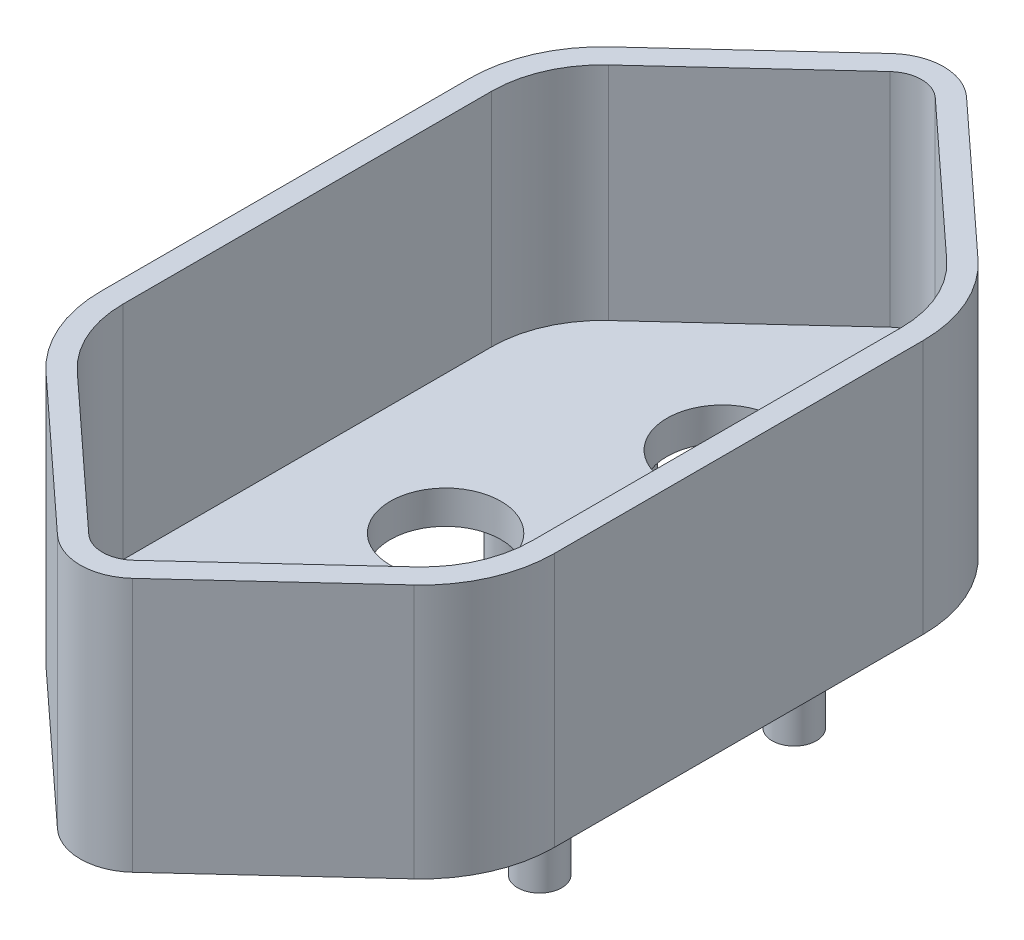
SolidWorks part; units mm, degrees
ref_plane "Plano frontal" through (0, 0, 0) normal (0, 0, 1) x (1, 0, 0)
ref_plane "Plano superior" through (0, 0, 0) normal (0, 1, 0) x (1, 0, 0)
ref_plane "Plano direito" through (0, 0, 0) normal (1, 0, 0) x (0, 0, -1)
sketch "Esboço1" plane through (0, 0, 0) normal (0, 1, 0) x (1, 0, 0)
  line L1 (-13.35, 19.65) -> (13.35, 19.65)
  line L2 (-13.35, 19.65) -> (-13.35, -19.65)
  line L3 (-13.35, -19.65) -> (13.35, -19.65)
  line L4 (13.35, 19.65) -> (13.35, -19.65)
  line L5 (-13.35, 19.65) -> (13.35, -19.65) construction
  line L6 (-13.35, -19.65) -> (13.35, 19.65) construction
  point P0 (0, 0)
  dimension "D1" = 26.7
  dimension "D2" = 39.3
extrude "Ressalto-extrusão1" add sketch "Esboço1" against normal blind 38.5
sketch "Esboço2" plane through (0, 0, 0) normal (0, 1, 0) x (1, 0, 0)
  line L0 (0, -19.04) -> (0, 19.04) construction
  line L1 (1.0166, -18.1029) -> (7.6387, -11.9991)
  line L2 (9.25, -8.3226) -> (9.25, 8.3226)
  line L3 (7.6387, 11.9991) -> (1.0166, 18.1029)
  line L4 (0, 0) -> (9.25, 0) construction
  line L5 (-1.0166, -18.1029) -> (-7.6387, -11.9991)
  line L6 (-7.6387, 11.9991) -> (-1.0166, 18.1029)
  line L7 (-9.25, -8.3226) -> (-9.25, 8.3226)
  arc A0 (9.25, 8.3226) -> (7.6387, 11.9991) centre (4.25, 8.3226) ccw
  arc A1 (7.6387, -11.9991) -> (9.25, -8.3226) centre (4.25, -8.3226) ccw
  arc A2 (-7.6387, -11.9991) -> (-9.25, -8.3226) centre (-4.25, -8.3226) cw
  arc A3 (-9.25, 8.3226) -> (-7.6387, 11.9991) centre (-4.25, 8.3226) cw
  arc A4 (1.0166, 18.1029) -> (-1.0166, 18.1029) centre (0, 17) ccw
  arc A5 (1.0166, -18.1029) -> (-1.0166, -18.1029) centre (0, -17) cw
  point P3 (0, 0)
  dimension "D1" = 5
  dimension "D2" = 1.5
  dimension "D3" = 37
  dimension "D4" = 28
  dimension "D5" = 18.5
extrude "Corte-extrusão1" cut sketch "Esboço2" against normal blind 10 contours A5 L1 A1 L2 A0 L3 A4 L6 A3 L7 A2 L5
sketch "Esboço4" plane through (0, 0, 0) normal (0, 1, 0) x (1, 0, 0)
  line L14 (-8.3165, -12.7344) -> (-1.6944, -18.8382)
  line L15 (1.6944, -18.8382) -> (8.3165, -12.7344)
  line L16 (10.25, -8.3226) -> (10.25, 8.3226)
  line L17 (8.3165, 12.7344) -> (1.6944, 18.8382)
  line L18 (-1.6944, 18.8382) -> (-8.3165, 12.7344)
  line L19 (-10.25, 8.3226) -> (-10.25, -8.3226)
  line L20 (1.0166, -18.1029) -> (7.6387, -11.9991)
  line L21 (9.25, -8.3226) -> (9.25, 8.3226)
  line L22 (7.6387, 11.9991) -> (1.0166, 18.1029)
  line L23 (-1.0166, 18.1029) -> (-7.6387, 11.9991)
  line L24 (-9.25, 8.3226) -> (-9.25, -8.3226)
  line L25 (-7.6387, -11.9991) -> (-1.0166, -18.1029)
  line L26 (1.0166, -18.1029) -> (7.6387, -11.9991)
  line L27 (9.25, -8.3226) -> (9.25, 8.3226)
  line L28 (7.6387, 11.9991) -> (1.0166, 18.1029)
  line L29 (-1.0166, 18.1029) -> (-7.6387, 11.9991)
  line L30 (-9.25, 8.3226) -> (-9.25, -8.3226)
  line L31 (-7.6387, -11.9991) -> (-1.0166, -18.1029)
  line L36 (13.35, -19.65) -> (13.35, 19.65)
  line L37 (13.35, 19.65) -> (-13.35, 19.65)
  line L38 (-13.35, 19.65) -> (-13.35, -19.65)
  line L39 (-13.35, -19.65) -> (13.35, -19.65)
  line L40 (13.35, -19.65) -> (13.35, 19.65)
  line L41 (13.35, 19.65) -> (-13.35, 19.65)
  line L42 (-13.35, 19.65) -> (-13.35, -19.65)
  line L43 (-13.35, -19.65) -> (13.35, -19.65)
  arc A6 (-10.25, -8.3226) -> (-8.3165, -12.7344) centre (-4.25, -8.3226) ccw
  arc A7 (-1.6944, -18.8382) -> (1.6944, -18.8382) centre (0, -17) ccw
  arc A8 (8.3165, -12.7344) -> (10.25, -8.3226) centre (4.25, -8.3226) ccw
  arc A9 (10.25, 8.3226) -> (8.3165, 12.7344) centre (4.25, 8.3226) ccw
  arc A10 (1.6944, 18.8382) -> (-1.6944, 18.8382) centre (0, 17) ccw
  arc A11 (-8.3165, 12.7344) -> (-10.25, 8.3226) centre (-4.25, 8.3226) ccw
  arc A12 (7.6387, -11.9991) -> (9.25, -8.3226) centre (4.25, -8.3226) ccw
  arc A13 (9.25, 8.3226) -> (7.6387, 11.9991) centre (4.25, 8.3226) ccw
  arc A14 (1.0166, 18.1029) -> (-1.0166, 18.1029) centre (0, 17) ccw
  arc A15 (-7.6387, 11.9991) -> (-9.25, 8.3226) centre (-4.25, 8.3226) ccw
  arc A16 (-9.25, -8.3226) -> (-7.6387, -11.9991) centre (-4.25, -8.3226) ccw
  arc A17 (-1.0166, -18.1029) -> (1.0166, -18.1029) centre (0, -17) ccw
  arc A18 (7.6387, -11.9991) -> (9.25, -8.3226) centre (4.25, -8.3226) ccw
  arc A19 (9.25, 8.3226) -> (7.6387, 11.9991) centre (4.25, 8.3226) ccw
  arc A20 (1.0166, 18.1029) -> (-1.0166, 18.1029) centre (0, 17) ccw
  arc A21 (-7.6387, 11.9991) -> (-9.25, 8.3226) centre (-4.25, 8.3226) ccw
  arc A22 (-9.25, -8.3226) -> (-7.6387, -11.9991) centre (-4.25, -8.3226) ccw
  arc A23 (-1.0166, -18.1029) -> (1.0166, -18.1029) centre (0, -17) ccw
  line M41 (13.35, -19.65) -> (13.35, 19.65)
  line M42 (13.35, 19.65) -> (-13.35, 19.65)
  line M43 (-13.35, 19.65) -> (-13.35, -19.65)
  line M44 (-13.35, -19.65) -> (13.35, -19.65)
  dimension "D1" = 0
  dimension "D2" = 1
  dimension "D3" = 0
extrude "Corte-extrusão2" cut sketch "Esboço4" against normal blind 10 contours A11 L18 A10 L17 A9 L16 A8 L15 A7 L14 A6 L19 M44 M41 M42 M43 region at (0, 0, 19.6025)
sketch "Esboço5" plane through (0, -38.5, 0) normal (0, -1, 0) x (1, 0, 0)
  line L1 (11.3, -13.5) -> (-11.3, -13.5)
  line L2 (11.3, -13.5) -> (11.3, 13.5)
  line L3 (11.3, 13.5) -> (-11.3, 13.5)
  line L4 (-11.3, -13.5) -> (-11.3, 13.5)
  line L5 (11.3, -13.5) -> (-11.3, 13.5) construction
  line L6 (11.3, 13.5) -> (-11.3, -13.5) construction
  line L10 (13.35, -19.65) -> (13.35, 19.65)
  line L11 (13.35, 19.65) -> (-13.35, 19.65)
  line L12 (-13.35, 19.65) -> (-13.35, -19.65)
  line L13 (-13.35, -19.65) -> (13.35, -19.65)
  line L14 (13.35, -19.65) -> (13.35, 19.65)
  line L15 (13.35, 19.65) -> (-13.35, 19.65)
  line L16 (-13.35, 19.65) -> (-13.35, -19.65)
  line L17 (-13.35, -19.65) -> (13.35, -19.65)
  point P0 (0, 0)
  line M3 (13.35, -19.65) -> (13.35, 19.65)
  line M4 (13.35, 19.65) -> (-13.35, 19.65)
  line M5 (-13.35, 19.65) -> (-13.35, -19.65)
  line M6 (-13.35, -19.65) -> (13.35, -19.65)
  dimension "D1" = 27
  dimension "D2" = 22.6
  dimension "D3" = 0
extrude "Corte-extrusão4" cut sketch "Esboço5" against normal blind 27 contours L1 L4 L3 L2 M6 M3 M4 M5 region at (0, -38.5, -19.1749)
sketch "Esboço6" plane through (0, -10, 0) normal (0, 1, 0) x (1, 0, 0)
  line L0 (0, -9.5) -> (0, 9.5) construction
  line L1 (0, 0) -> (-3, 0) construction
  circle A0 centre (0, -9.5) radius 2.5
  circle A1 centre (0, 9.5) radius 2.5
  circle A2 centre (-3, 0) radius 2.5
  point P3 (0, 0)
  dimension "D1" = 5
  dimension "D2" = 19
  dimension "D3" = 3
extrude "Corte-extrusão5" cut sketch "Esboço6" against normal blind 5
sketch "Esboço7" plane through (0, -11.5, 0) normal (0, -1, 0) x (1, 0, 0)
  line L0 (13.35, -19.65) -> (13.35, 19.65) construction
  line L1 (11.3, 13.5) -> (13.35, 13.5)
  line L2 (11.3, 13.5) -> (11.3, 12.5)
  line L3 (11.3, 12.5) -> (13.35, 12.5)
  line L4 (13.35, 13.5) -> (13.35, 12.5)
  line L5 (0, 0) -> (0, 13.5) construction
  line L6 (11.3, 13.5) -> (-11.3, 13.5) construction
  line L7 (0, 0) -> (11.3, 0) construction
  line L8 (11.3, -13.5) -> (11.3, 13.5) construction
  line L9 (-13.35, 13.5) -> (-13.35, 12.5)
  line L10 (-11.3, 12.5) -> (-13.35, 12.5)
  line L11 (-11.3, 13.5) -> (-11.3, 12.5)
  line L12 (-11.3, 13.5) -> (-13.35, 13.5)
  line L13 (-11.3, -13.5) -> (-13.35, -13.5)
  line L14 (-11.3, -13.5) -> (-11.3, -12.5)
  line L15 (-11.3, -12.5) -> (-13.35, -12.5)
  line L16 (-13.35, -13.5) -> (-13.35, -12.5)
  line L17 (13.35, -13.5) -> (13.35, -12.5)
  line L18 (11.3, -12.5) -> (13.35, -12.5)
  line L19 (11.3, -13.5) -> (11.3, -12.5)
  line L20 (11.3, -13.5) -> (13.35, -13.5)
  dimension "D1" = 1
extrude "Ressalto-extrusão2" add sketch "Esboço7" along normal blind 4
sketch "Sketch2" plane through (11.3, 0, 0) normal (1, 0, 0) x (0, 0, -1)
  line L6 (-13.5, -11.5) -> (13.5, -11.5)
  line L7 (-13.5, -11.5) -> (-13.5, -38.5)
  line L8 (-13.5, -38.5) -> (13.5, -38.5)
  line L9 (13.5, -11.5) -> (13.5, -38.5)
extrude "Cut-Extrude1" cut sketch "Sketch2" against normal blind 100 and the other way blind 10
extrude "Cut-Extrude3" cut sketch "Esboço4<3>" against normal blind 100 contours A11 L18 A10 L17 A9 L16 A8 L15 A7 L14 A6 L19 M44 M41 M42 M43 region at (0, 0, 19.6025)
sketch "Esboço4<3>" plane through (0, 0, 0) normal (0, 1, 0) x (1, 0, 0) same geometry as "Esboço4"
sketch "Sketch6" plane through (0, -11.5, 0) normal (0, -1, 0) x (1, 0, 0)
  line L0 (-3.55, 2.4387) -> (-3.55, 13.2)
  line L1 (3.55, -8) -> (3.55, 8)
  line L2 (3.55, -8) -> (9, -8)
  line L3 (9, -8) -> (9, 8)
  line L4 (3.55, 8) -> (9, 8)
  line L5 (-3.55, -13.2) -> (-3.55, -2.4387)
  line L6 (-3.55, -13.2) -> (3.55, -13.2)
  line L7 (3.55, -13.2) -> (3.55, 13.2)
  line L8 (-3.55, 13.2) -> (3.55, 13.2)
  line L9 (-2.75, -12.4) -> (-2.75, -3.2905)
  line L10 (-2.75, -12.4) -> (2.75, -12.4)
  line L11 (2.75, -12.4) -> (2.75, -0.4)
  line L12 (0.2757, -0.4) -> (2.75, -0.4)
  line L13 (2.75, 0.4) -> (2.75, 12.4)
  line L14 (2.75, 0.4) -> (0.2757, 0.4)
  line L15 (-2.75, 3.2905) -> (-2.75, 12.4)
  line L16 (2.75, 12.4) -> (-2.75, 12.4)
  line L17 (3.55, 0) -> (-14.2868, 0) construction
  line L18 (-3.55, 13.2) -> (-7.55, 13.2)
  line L19 (-3.55, 13.2) -> (-3.55, 3.2)
  line L20 (-3.55, 3.2) -> (-7.55, 3.2)
  line L21 (-7.55, 13.2) -> (-7.55, 3.2)
  line L22 (-3.55, -13.2) -> (-7.55, -13.2)
  line L23 (-3.55, -13.2) -> (-3.55, -3.2)
  line L24 (-3.55, -3.2) -> (-7.55, -3.2)
  line L25 (-7.55, -13.2) -> (-7.55, -3.2)
  circle A0 centre (7, -5.75) radius 1
  circle A1 centre (7, 5.75) radius 1
  arc A2 (-3.55, -2.4387) -> (-3.55, 2.4387) centre (-3, 0) ccw
  arc A3 (-2.75, -3.2905) -> (0.2757, -0.4) centre (-3, 0) ccw
  arc A4 (0.2757, 0.4) -> (-2.75, 3.2905) centre (-3, 0) ccw
  circle A5 centre (-5.55, 5.7) radius 1
  circle A6 centre (-5.55, 10.7) radius 1
  circle A7 centre (-5.55, -5.7) radius 1
  circle A8 centre (-5.55, -10.7) radius 1
  dimension "D1" = 4
  dimension "D2" = 4
  dimension "D3" = 10
  dimension "D4" = 10
extrude "Boss-Extrude5" add sketch "Sketch6" along normal blind 4 contours A6 | A7 | A8 | A1 | A0 | A5 region at (-5.55, -11.5, 10.7) region at (-5.55, -11.5, -5.7) region at (-5.55, -11.5, -10.7)
